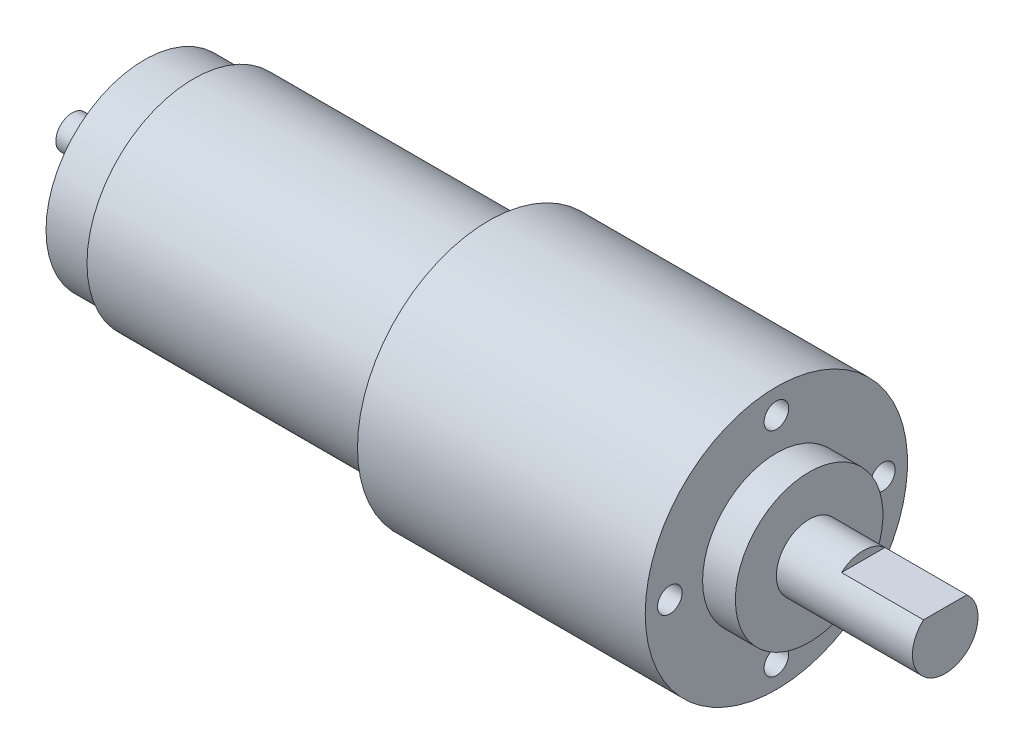
SolidWorks part; units mm, degrees
ref_plane "Plan de face" through (0, 0, 0) normal (0, 0, 1) x (1, 0, 0)
ref_plane "Plan de dessus" through (0, 0, 0) normal (0, 1, 0) x (1, 0, 0)
ref_plane "Plan de droite" through (0, 0, 0) normal (1, 0, 0) x (0, 0, -1)
ref_axis "Axe1" through (-5.325, 0, 0) along (1, 0, 0)
sketch "Esquisse1" plane through (0, 0, 0) normal (0, 0, 1) x (1, 0, 0)
  line L0 (0, 0) -> (106.5, 0)
  line L1 (106.5, 0) -> (106.5, 4)
  line L2 (106.5, 4) -> (89.9, 4)
  line L3 (89.9, 4) -> (89.9, 9)
  line L4 (89.9, 9) -> (85.9, 9)
  line L5 (85.9, 9) -> (85.9, 16)
  line L6 (85.9, 16) -> (50.8, 16)
  line L7 (50.8, 16) -> (50.8, 13)
  line L8 (50.8, 13) -> (14.8, 13)
  line L9 (14.8, 13) -> (14.8, 12)
  line L10 (14.8, 12) -> (8.8, 12)
  line L11 (8.8, 12) -> (8.8, 2)
  line L12 (8.8, 2) -> (0, 2)
  line L13 (0, 2) -> (0, 0)
  dimension "D1" = 35.1
  dimension "D2" = 4
  dimension "D3" = 20.6
  dimension "D4" = 13
  dimension "D5" = 16
  dimension "D6" = 9
  dimension "D7" = 12
  dimension "D8" = 2
  dimension "D9" = 42
  dimension "D10" = 6
  dimension "D11" = 8.8
  dimension "D12" = 4
  dimension "D13" = 106.5
revolve "Révolution1" add sketch "Esquisse1" angle 360 about L0
sketch "Esquisse2" plane through (106.5, 0, 0) normal (1, 0, 0) x (0, 0, -1)
  line L1 (-2.6458, 3) -> (2.6458, 3)
  line L2 (-2.6458, 3) -> (-2.6458, 4)
  line L3 (-2.6458, 4) -> (2.6458, 4)
  line L4 (2.6458, 3) -> (2.6458, 4)
  circle A0 centre (0, 0) radius 4 construction
  circle A1 centre (0, 0) radius 4 construction
  dimension "D1" = 1
extrude "Enlèv. mat.-Extru.1" cut sketch "Esquisse2" against normal blind 10
sketch "Esquisse3" plane through (85.9, 0, 0) normal (1, 0, 0) x (0, 0, -1)
  line L0 (0, 17.6) -> (0, -17.6) construction
  circle A0 centre (0, 13) radius 1.5
  circle A1 centre (0, 0) radius 16 construction
  dimension "D1" = 3
  dimension "D2" = 13
extrude "Enlèv. mat.-Extru.2" cut sketch "Esquisse3" against normal blind 3
pattern_circular "Répétition circulaire1" count 4 every 90 about axis through (-5.325, 0, 0) along (1, 0, 0) of "Enlèv. mat.-Extru.2"
